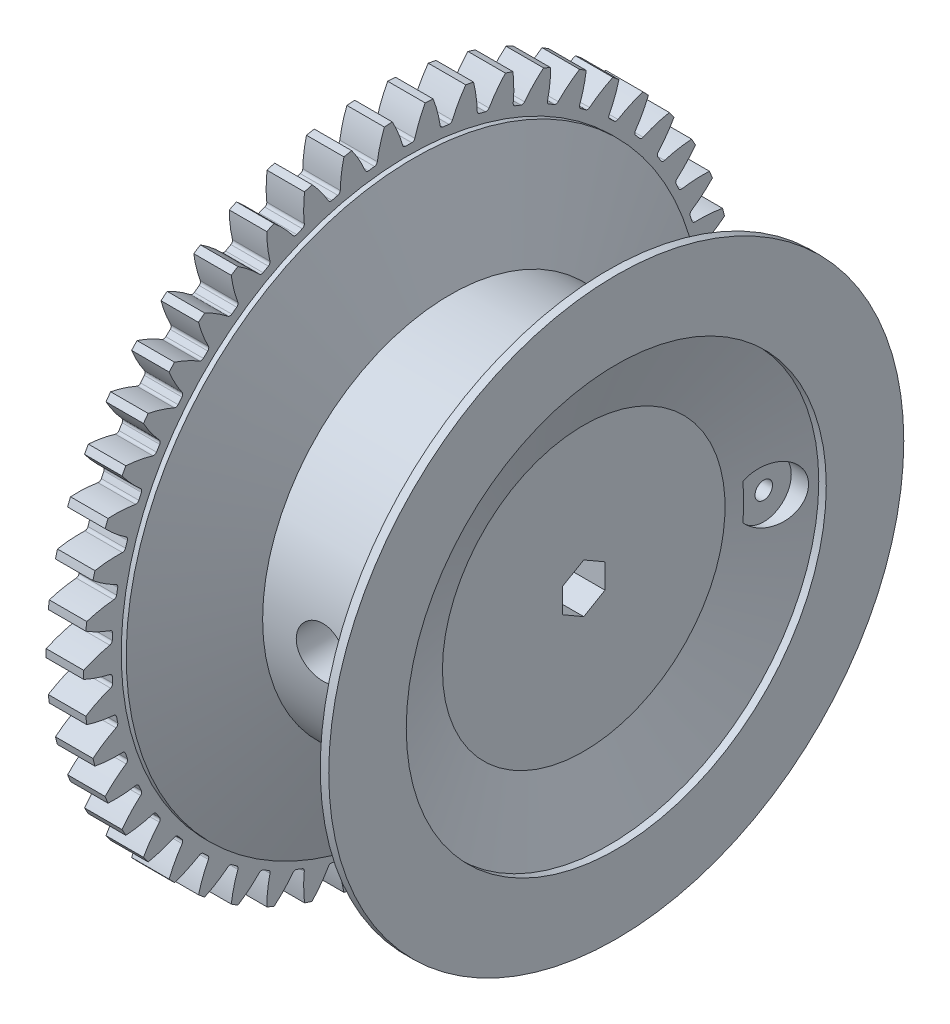
SolidWorks part; units mm, degrees
other "FixedAxisReel" parameters "Num_teeth"=50, "Thickness"=1.5, "D2"=57.0673, "D3"=57.0673, "D1"=33.7821, "Fillet_rad"=0.635, "h"=15.875, "G1"=0.635, "G2"=0.635, "H2"=13.4937, "D4"=80.6935, "Diameter"=80.0795, "D5"=22.4032, "H1"=13.4937, "D6"=30, "MHD"=25.4, "MHD_radius"=12.7
material "Nylon 101"
ref_plane "Plane1" through (0, 0, 0) normal (0, 0, 1) x (1, 0, 0)
ref_plane "Plane2" through (0, 0, 0) normal (0, 1, 0) x (1, 0, 0)
ref_plane "Plane3" through (0, 0, 0) normal (1, 0, 0) x (0, 0, -1)
sketch "BasProSke" plane through (0, 0, 0) normal (0, 1, 0) x (1, 0, 0)
  line L0 (-10, 0) -> (60, 0) construction
  line L1 (0, 0) -> (0, 13)
  line L2 (0, 0) -> (1.5, 0)
  line L3 (1.5, 0) -> (1.5, 13)
  line L4 (1.5, 13) -> (0, 13)
  dimension "Thickness" = 1.5
  dimension "Diameter" = 26
revolve "Base-Revolve" add sketch "BasProSke" angle 360 about L0
sketch "TooCutSke" plane through (0, 0, 0) normal (1, 0, 0) x (0, 0, -1)
  line L1 (0, 0) -> (0, 107) construction
  line L2 (0, 0) -> (-0.4259, 12.4927) construction
  line L3 (0, 0) -> (-1.5691, 24.9404) construction
  line L4 (-0.4259, 12.4927) -> (-0.7846, 12.4702) construction
  arc A0 (0.2187, 11.872) -> (-0.2187, 11.872) centre (0, 0) ccw
  arc A1 (0.6715, 13.0081) -> (-0.6715, 13.0081) centre (0, 0) ccw
  circle A2 centre (0, 0) radius 12.5 construction
  circle A3 centre (0, 0) radius 11.7462 construction
  arc A4 (-0.2187, 11.872) -> (-0.6715, 13.0081) centre (-5.0549, 10.6028) ccw
  arc A5 (0.6715, 13.0081) -> (0.2187, 11.872) centre (5.0549, 10.6028) ccw
  dimension "Root_dia" = 23.748
  dimension "Overcut_dia" = 26.0508
  dimension "Pitch_dia" = 25
  dimension "Base_dia" = 23.4923
  dimension "Flank_rad" = 5
  dimension "Half_ang" = 3.6
  dimension "Half_CT" = 0.3594
extrude "ToothCut" cut sketch "TooCutSke" along normal through all
fillet "RootFillets" radius 0.126 2 edges at (0.75, 11.872, -0.2187) (0.75, 11.872, 0.2187)
pattern_circular "TeethCuts" count 50 every 7.2 about axis through (-10, 0, 0) along (1, 0, 0) of "ToothCut", "RootFillets"
ref_plane "FarPln" through (1.5, 0, 0) normal (1, 0, 0) x (0, 0, -1)
sketch "ReelSke" plane through (0, 0, 0) normal (0, 1, 0) x (1, 0, 0)
  line L0 (1.5, 11.5) -> (1.7, 11.5)
  line L1 (1.7, 11.5) -> (3.7018, 6)
  line L2 (3.7018, 6) -> (7.2982, 6)
  line L3 (7.2982, 6) -> (9.3, 11.5)
  line L4 (9.3, 11.5) -> (9.5, 11.5)
  line L5 (9.5, 11.5) -> (9.5, 0)
  line L6 (9.5, 0) -> (1.5, 0)
  line L7 (1.5, -0.1216) -> (1.5, 0.1216) construction
  line L8 (1.5, 11.5) -> (1.5, 0)
  line L9 (5.5, 0) -> (5.5, 6) construction
  point P12 (5.5, 6)
  point P13 (5.5, 0)
  dimension "D1" = 70
  dimension "D2" = 0.2
  dimension "D3" = 6
  dimension "D4" = 8
  dimension "D5" = 11.5
revolve "Reel" add sketch "ReelSke" angle 360 about L6
sketch "ScrewHole2Ske" plane through (0, 0, 0) normal (0, 0, 1) x (1, 0, 0)
  line L0 (3.7018, 0) -> (7.2982, 0) construction
  line L1 (3.7018, 6) -> (3.7018, -6) construction
  line L2 (7.2982, 6) -> (7.2982, -6) construction
  circle A0 centre (5.5, 0) radius 1
  point P9 (5.5, 0)
  dimension "D1" = 2
sketch "ShaftHoleSke" plane through (0, 0, 0) normal (-1, 0, 0) x (0, 0, 1)
  line L1 (0.85, 0.4907) -> (0, 0.9815)
  line L2 (0, 0.9815) -> (-0.85, 0.4907)
  line L3 (-0.85, 0.4907) -> (-0.85, -0.4907)
  line L4 (-0.85, -0.4907) -> (0, -0.9815)
  line L5 (0, -0.9815) -> (0.85, -0.4907)
  line L6 (0.85, -0.4907) -> (0.85, 0.4907)
  circle A2 centre (0, 0) radius 0.85 construction
  dimension "D1" = 1.7
extrude "ShaftHole" cut sketch "ShaftHoleSke" against normal through all both and the other way through all
sketch "CutSke" plane through (0, 0, 0) normal (0, 1, 0) x (1, 0, 0)
  line L0 (0, 8.3999) -> (1.5, 8.3999)
  line L1 (3.7018, 6) -> (1.7, 11.5) construction
  line L2 (1.5, -11.5) -> (1.5, 11.5) construction
  line L3 (1.5, 8.3999) -> (2.5, 5.6524)
  line L5 (2.5, 5.6524) -> (2.5, 0)
  line L8 (3.7018, 6) -> (1.7, 11.5) construction
  line L9 (0, 0) -> (0, 8.3999)
  line L11 (9.5, 8.3999) -> (8.5, 5.6524)
  line L12 (9.5, -11.5) -> (9.5, 11.5) construction
  line L14 (8.5, 5.6524) -> (8.5, 0)
  line L15 (8.5, 0) -> (9.5, 0)
  line L16 (9.5, 0) -> (9.5, 8.3999)
  line L17 (0, 0.1216) -> (0, -0.1216) construction
  line L18 (0, 0) -> (2.5, 0)
  dimension "D1" = 1.2482
  dimension "D2" = 8.5
  dimension "D3" = 2.5
revolve "Cut" cut sketch "CutSke" angle 360 about L18
sketch "PadSke" plane through (2.5, 0, 0) normal (-1, 0, 0) x (0, 0, 1)
  line L1 (-0.85, 0.4907) -> (-0.85, -0.4907)
  line L2 (-0.85, -0.4907) -> (0, -0.9815)
  line L3 (0, -0.9815) -> (0.85, -0.4907)
  line L4 (0.85, -0.4907) -> (0.85, 0.4907)
  line L5 (0.85, 0.4907) -> (0, 0.9815)
  line L6 (0, 0.9815) -> (-0.85, 0.4907)
  circle A0 centre (0, 0) radius 2
  circle A2 centre (0, 0) radius 0.85 construction
  dimension "D1" = 4
extrude "Pad" add sketch "PadSke" along normal blind 1.5
sketch "ScrewHoleSke" plane through (9.5, 0, 0) normal (1, 0, 0) x (0, 0, -1)
  circle A0 centre (7, 0) radius 0.35
  dimension "D1" = 7
  dimension "D2" = 0.7
extrude "ScrewHole" cut sketch "ScrewHoleSke" against normal through all both and the other way through all
sketch "Pad2Ske" plane through (9.5, 0, 0) normal (1, 0, 0) x (0, 0, -1)
  circle A0 centre (7, 0) radius 1.1
  circle A1 centre (7, 0) radius 0.35 construction
  dimension "D1" = 2.2
extrude "Pad2" cut sketch "Pad2Ske" against normal blind 0.8
ref_plane "Plane" through (5.5, 0, 0) normal (1, 0, 0) x (0, 0, -1)
mirror "Pad3" about plane through (5.5, 0, 0) normal (1, 0, 0) of "Pad2"
sketch "BoldSke" plane through (0, 0, 0) normal (0, 1, 0) x (1, 0, 0)
  line L0 (3.7018, -6) -> (7.2982, -6)
  line L1 (7.2982, -6) -> (7.8441, -7.5)
  line L2 (7.2982, -6) -> (9.3, -11.5) construction
  line L3 (7.8441, -7.5) -> (3.1559, -7.5)
  line L4 (3.1559, -7.5) -> (3.7018, -6)
  line L5 (1.7, -11.5) -> (3.7018, -6) construction
  line L6 (0, 0) -> (15.2765, 0) construction
  dimension "D1" = 1.5
revolve "Bold" add sketch "BoldSke" angle 330 mid plane about L6
extrude "ScrewHole2" cut sketch "ScrewHole2Ske" along normal through all
sketch "WidenSke" plane through (0, 0, 0) normal (0, 1, 0) x (1, 0, 0)
  line L0 (9.5, 8.3999) -> (9.8, 8.3999)
  line L1 (9.8, 8.3999) -> (9.8, 11.5)
  line L2 (9.8, 11.5) -> (9.5, 11.5)
  line L3 (9.5, 11.5) -> (9.5, 8.3999)
  dimension "D1" = 0.3
revolve "Widen" add sketch "WidenSke" angle 360 about L0
chamfer "Chamfer" distance 0.8 angle 10 1 edges at (9.3, 0, -11.5) first distance on face at (7.5711, 0, -2.885)
equation "\"Num_teeth@TeethCuts\" = ((sgn( \"Num_teeth@TeethCuts\" - 2.0)+1)*( \"Num_teeth@TeethCuts\" - 2.0))/2 +2.0"
equation "\"Thickness@FarPln\" = \"Thickness@BasProSke\""
